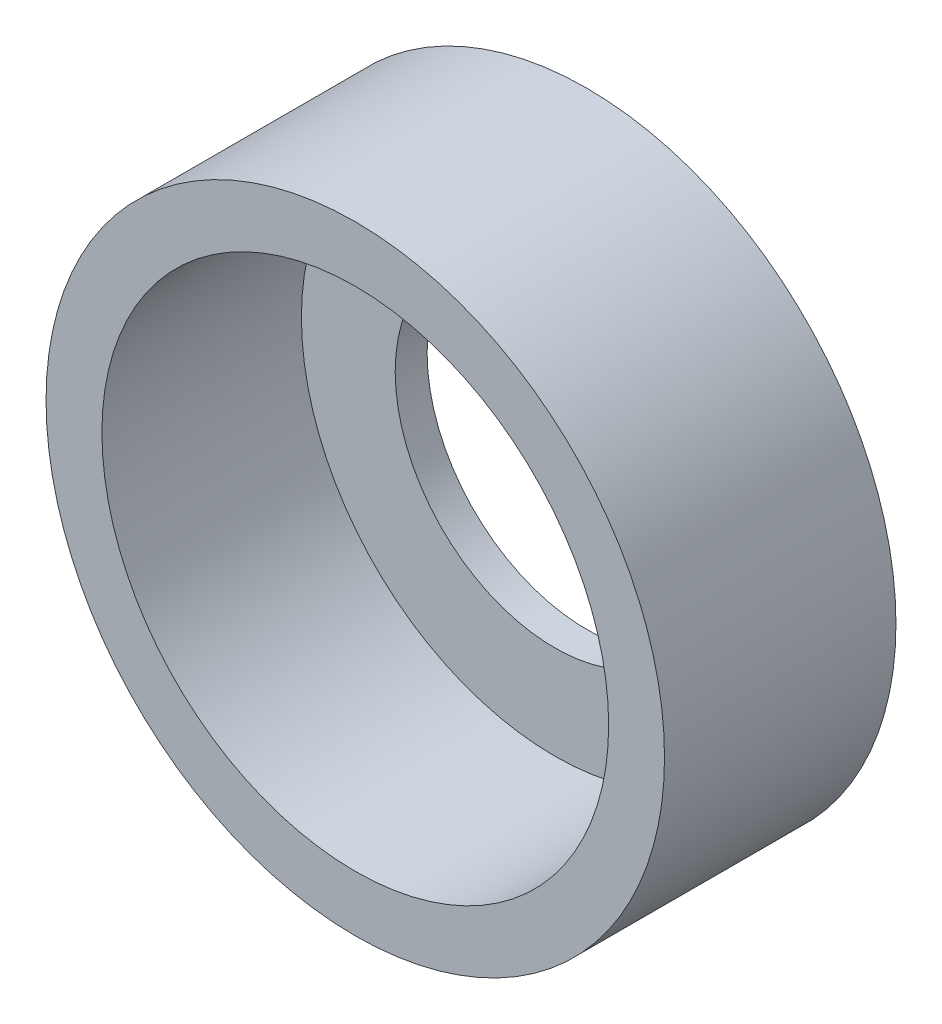
SolidWorks part; units mm, degrees
ref_plane "Front Plane" through (0, 0, 0) normal (1, 0, 0) x (0, 1, 0)
ref_plane "Top Plane" through (0, 0, 0) normal (0, 0, 1) x (0, 1, 0)
ref_plane "Right Plane" through (0, 0, 0) normal (0, 1, 0) x (-1, 0, 0)
ref_axis "x axis" through (-88.99, 0, 0) along (1, 0, 0)
ref_axis "y xxis" through (0, 88.99, 0) along (0, -1, 0)
ref_axis "z axis" through (0, 0, 55) along (0, 0, -1)
sketch "Sketch1" plane through (0, 0, 0) normal (0, 0, 1) x (0, 1, 0)
  circle A0 centre (0, 0) radius 2
  circle A1 centre (0, 0) radius 3.875
  circle A2 centre (0, 0) radius 3.175 construction
  dimension "D1" = 6.35
  dimension "D2" = 0.7
  dimension "D3" = 4
extrude "Boss-Extrude1" add sketch "Sketch1" along normal blind 0.4
sketch "Sketch2" plane through (0, 0, 0.4) normal (0, 0, 1) x (1, 0, 0)
  circle A0 centre (0, 0) radius 3.175
  circle A1 centre (0, 0) radius 3.875
  circle A2 centre (0, 0) radius 3.175 construction
  circle A3 centre (0, 0) radius 3.875 construction
extrude "Boss-Extrude2" add sketch "Sketch2" along normal blind 2.5
